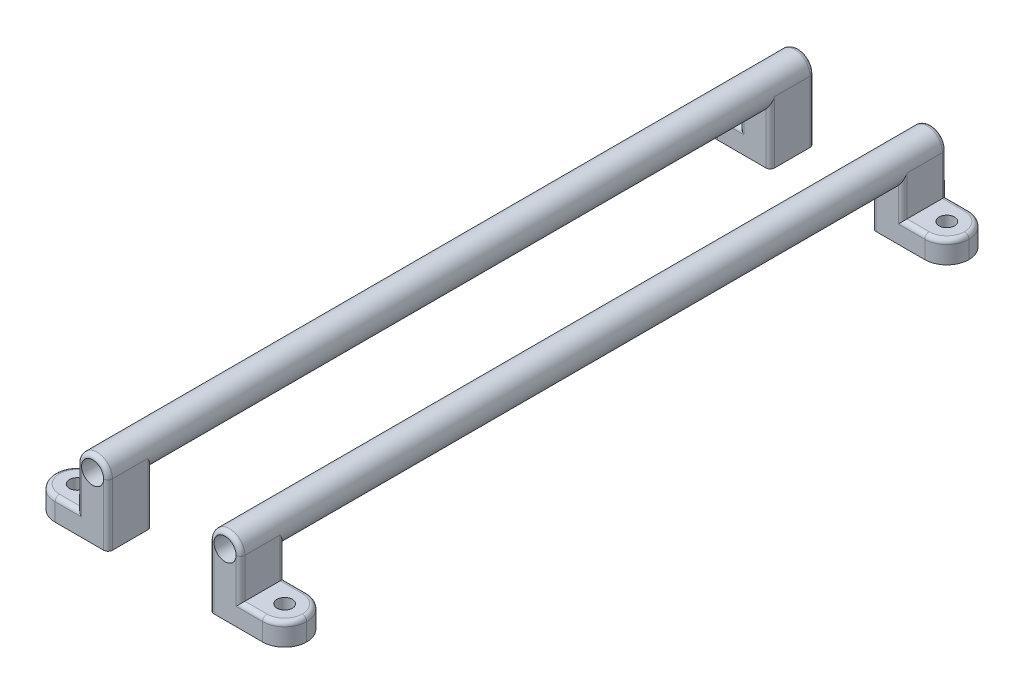
SolidWorks part; units mm, degrees
ref_plane "Front Plane" through (0, 0, 0) normal (0, 0, 1) x (1, 0, 0)
ref_plane "Top Plane" through (0, 0, 0) normal (0, 1, 0) x (1, 0, 0)
ref_plane "Right Plane" through (0, 0, 0) normal (1, 0, 0) x (0, 0, -1)
sketch "Sketch1" plane through (0, 0, 0) normal (0, 0, 1) x (1, 0, 0)
  circle A0 centre (-15, 0) radius 2.5
  circle A1 centre (15, 0) radius 2.5
  circle A2 centre (-15, 0) radius 3.5
  circle A3 centre (15, 0) radius 3.5
  dimension "D3" = 5
  dimension "D4" = 7
  dimension "D1" = 15
  dimension "D2" = 15
extrude "Boss-Extrude1" add sketch "Sketch1" along normal blind 10 and the other way blind 150
sketch "Sketch2" plane through (0, 0, 0) normal (0, 0, 1) x (1, 0, 0)
  line L0 (-18.5, 0) -> (-18.5, -9)
  line L2 (-11.5, 0) -> (-11.5, -14)
  line L5 (11.5, 0) -> (11.5, -14)
  line L6 (18.5, 0) -> (18.5, -9)
  line L9 (-18.5, -9) -> (-28.5, -9)
  line L10 (-28.5, -9) -> (-28.5, -14)
  line L11 (-28.5, -14) -> (-11.5, -14)
  line L12 (18.5, -9) -> (28.5, -9)
  line L13 (11.5, -14) -> (28.5, -14)
  line L14 (28.5, -14) -> (28.5, -9)
  arc A0 (-18.5, 0) -> (-11.5, 0) centre (-15, 0) ccw
  circle A1 centre (-15, 0) radius 3.5 construction
  arc A2 (11.5, 0) -> (18.5, 0) centre (15, 0) ccw
  circle A3 centre (15, 0) radius 3.5 construction
  dimension "D1" = 5
  dimension "D2" = 14
  dimension "D3" = 10
extrude "Boss-Extrude2" add sketch "Sketch2" along normal up to surface (10 mm away) up to face at (-11.5, 0, 10)
sketch "Sketch4" plane through (0, 0, -150) normal (0, 0, -1) x (-1, 0, 0)
  line L0 (18.5, 0) -> (18.5, -9) construction
  line L1 (18.5, 0) -> (18.5, -9)
  line L2 (18.5, -9) -> (28.5, -9)
  line L3 (28.5, -9) -> (28.5, -14)
  line L4 (28.5, -14) -> (11.5, -14)
  line L5 (11.5, -14) -> (11.5, 0)
  line L6 (-11.5, 0) -> (-11.5, -14)
  line L7 (-11.5, -14) -> (-28.5, -14)
  line L8 (-28.5, -14) -> (-28.5, -9)
  line L9 (-28.5, -9) -> (-18.5, -9)
  line L10 (-18.5, -9) -> (-18.5, 0)
  arc A0 (-18.5, 0) -> (-11.5, 0) centre (-15, 0) ccw
  circle A1 centre (-15, 0) radius 3.5 construction
  arc A2 (11.5, 0) -> (18.5, 0) centre (15, 0) ccw
extrude "Boss-Extrude3" add sketch "Sketch4" against normal blind 10
sketch "Sketch5" plane through (0, -9, 0) normal (0, 1, 0) x (1, 0, 0)
  line L0 (-28.5, -10) -> (-28.5, 0) construction
  line L1 (-18.5, -10) -> (-28.5, -10) construction
  line L2 (28.5, -10) -> (28.5, 0) construction
  line L3 (-28.5, 140) -> (-18.5, 140) construction
  line L4 (-28.5, 140) -> (-28.5, 150) construction
  line L5 (28.5, 140) -> (28.5, 150) construction
  circle A0 centre (-23.5, -5) radius 1.75
  circle A1 centre (23.5, -5) radius 1.75
  circle A2 centre (-23.5, 145) radius 1.75
  circle A3 centre (23.5, 145) radius 1.75
  dimension "D1" = 3.5
  dimension "D7" = 3.5
  dimension "D2" = 5
  dimension "D3" = 5
  dimension "D4" = 5
  dimension "D5" = 5
  dimension "D6" = 5
  dimension "D8" = 5
extrude "Cut-Extrude1" cut sketch "Sketch5" against normal up to next
fillet "Fillet1" radius 5 4 edges at (-28.5, -11.5, -150) (-28.5, -11.5, -140) (-28.5, -11.5, 0) (-28.5, -11.5, 10)
fillet "Fillet2" radius 1 4 edges at (-18.5, -4.5, 10) (-15, 3.5, 10) (-11.5, -7, 0) (-11.5, -7, 10)
fillet "Fillet3" radius 1 4 edges at (-21, -9, 0) (-27.0355, -9, 1.4645) (-20.5, -9, 10) (-27.0355, -9, 8.5355)
fillet "Fillet4" radius 1 1 edges at (-18.5, -5, 0)
fillet "Fillet5" radius 1 9 edges at (-15, 3.5, -150) (-21, -9, -150) (-27.0355, -9, -148.5355) (-21, -9, -140) (-11.5, -7, -150) (-11.5, -7, -140) (-18.5, -4.5, -150) (-27.0355, -9, -141.4645) (-18.5, -4.5, -140)
fillet "Fillet6" radius 5 4 edges at (28.5, -11.5, -150) (28.5, -11.5, -140) (28.5, -11.5, 0) (28.5, -11.5, 10)
fillet "Fillet7" radius 1 18 edges at (21, -9, -140) (21, -9, -150) (27.0355, -9, -148.5355) (21, -9, 10) (21, -9, 0) (27.0355, -9, 1.4645) (18.5, -4.5, -150) (11.5, -7, -150) (18.5, -4.5, 10) (11.5, -7, 10) (27.0355, -9, -141.4645) (27.0355, -9, 8.5355) (18.5, -4.5, -140) (11.5, -7, -140) (11.5, -7, 0) (18.5, -4.5, 0) (15, 3.5, -150) (15, 3.5, 10)
